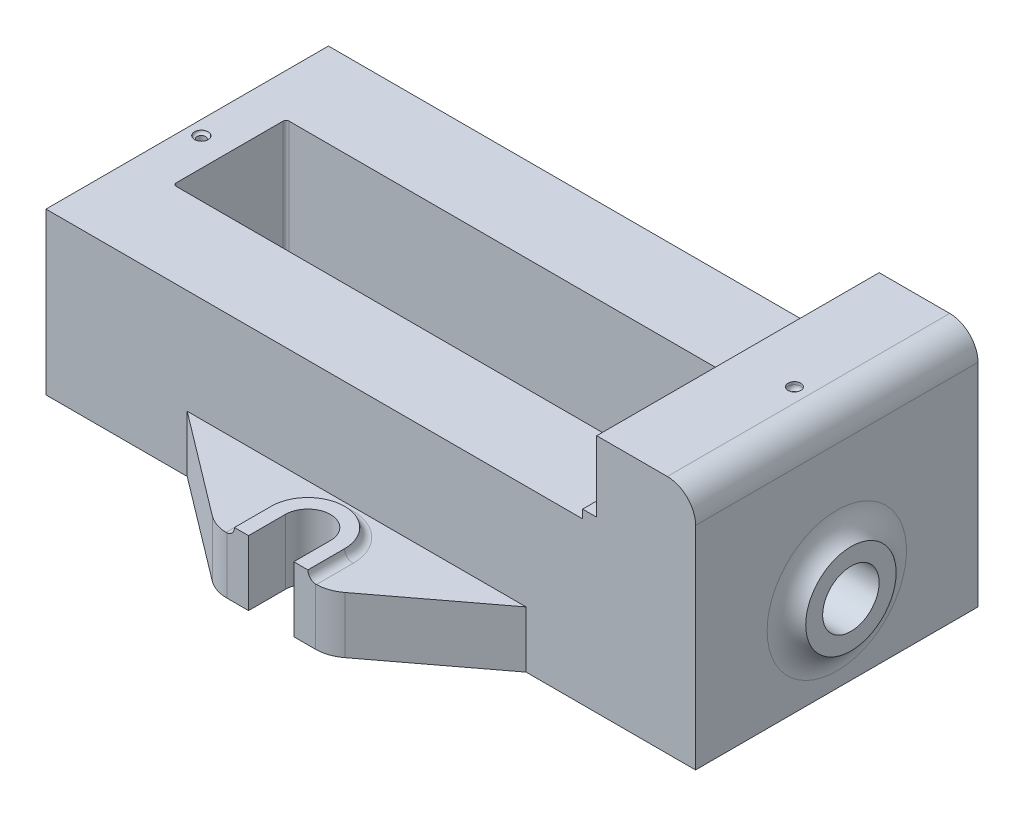
SolidWorks part; units mm, degrees
ref_plane "Front Plane" through (0, 0, 0) normal (0, 0, 1) x (1, 0, 0)
ref_plane "Top Plane" through (0, 0, 0) normal (0, 1, 0) x (1, 0, 0)
ref_plane "Right Plane" through (0, 0, 0) normal (1, 0, 0) x (0, 0, -1)
sketch "Sketch1" plane through (0, 0, 0) normal (0, 0, 1) x (1, 0, 0)
  line L0 (-148.8487, 0) -> (180.479, 0) construction
  line L1 (146.3044, 0) -> (146.3044, 75)
  line L2 (136.3044, 85) -> (111.3044, 85)
  line L3 (111.3044, 85) -> (111.3044, 60)
  line L4 (111.3044, 60) -> (106.3044, 60)
  line L5 (106.3044, 60) -> (106.3044, 57)
  line L6 (106.3044, 57) -> (-83.6956, 57)
  line L7 (-83.6956, 57) -> (-83.6956, 0)
  line L8 (-83.6956, 0) -> (146.3044, 0)
  arc A0 (136.3044, 85) -> (146.3044, 75) centre (136.3044, 75) cw
  point P13 (146.3044, 85)
  point P20 (153.9046, 30)
  dimension "D6" = 10
  dimension "D1" = 85
  dimension "D2" = 230
  dimension "D3" = 40
  dimension "D4" = 5
  dimension "D5" = 25
  dimension "D7" = 57
  dimension "D8" = 30
extrude "Boss-Extrude1" add sketch "Sketch1" along normal blind 100
sketch "Sketch2" plane through (146.3044, 0, 0) normal (1, 0, 0) x (0, 0, -1)
  line L0 (-100, 0) -> (0, 0) construction
  circle A0 centre (-50, 30) radius 16
  point P0 (-50, 0)
  dimension "D2" = 32
  dimension "D1" = 30
extrude "Boss-Extrude2" add sketch "Sketch2" along normal blind 5
fillet "Fillet1" radius 10 1 edges at (146.3044, 30, 66)
sketch "Sketch3" plane through (-83.6956, 0, 0) normal (-1, 0, 0) x (0, 0, 1)
  line L0 (50, 57) -> (50, 0) construction
  line L1 (100, 57) -> (0, 57) construction
  line L2 (100, 0) -> (0, 0) construction
  circle A1 centre (50, 30) radius 16
  dimension "D3" = 32
  dimension "D1" = 30
extrude "Boss-Extrude3" add sketch "Sketch3" along normal blind 5
fillet "Fillet2" radius 10 1 edges at (-83.6956, 46, 50)
sketch "Sketch4" plane through (-88.6956, 0, 0) normal (-1, 0, 0) x (0, 0, 1)
  circle A0 centre (50, 30) radius 5
  dimension "D1" = 10
extrude "Cut-Extrude1" cut sketch "Sketch4" against normal blind 20
sketch "Sketch5" plane through (0, 57, 0) normal (0, 1, 0) x (1, 0, 0)
  line L0 (-83.6956, -50) -> (106.3044, -50) construction
  line L1 (-83.6956, -100) -> (-83.6956, 0) construction
  line L2 (106.3044, -100) -> (106.3044, 0) construction
  line L4 (-67.6956, -30) -> (105.3044, -30)
  line L5 (-68.6956, -31) -> (-68.6956, -69)
  line L6 (-67.6956, -70) -> (105.3044, -70)
  line L7 (106.3044, -31) -> (106.3044, -69)
  line L8 (-68.6956, -30) -> (-68.1706, -30.12) construction
  line L9 (-68.6956, -70) -> (-68.1706, -69.88) construction
  line L10 (105.7794, -30.12) -> (106.3044, -30) construction
  line L11 (105.7794, -69.88) -> (106.3044, -70) construction
  arc A0 (106.3044, -31) -> (105.3044, -30) centre (105.3044, -31) ccw
  arc A1 (106.3044, -69) -> (105.3044, -70) centre (105.3044, -69) cw
  arc A2 (-67.6956, -70) -> (-68.6956, -69) centre (-67.6956, -69) cw
  arc A3 (-68.6956, -31) -> (-67.6956, -30) centre (-67.6956, -31) cw
  point P6 (18.8044, -50)
  dimension "D3" = 1
  dimension "D1" = 40
  dimension "D2" = 15
extrude "Cut-Extrude2" cut sketch "Sketch5" against normal through all
sketch "Sketch6" plane through (151.3044, 0, 0) normal (1, 0, 0) x (0, 0, -1)
  circle A0 centre (-50, 30) radius 10
  dimension "D1" = 20
extrude "Cut-Extrude3" cut sketch "Sketch6" against normal up to next
sketch "Sketch7" plane through (0, 0, 0) normal (0, -1, 0) x (1, 0, 0)
  line L0 (26.3044, 127.7371) -> (26.3044, -29.0287) construction
  line L3 (-88.6956, 66) -> (-88.6956, 34) construction
  line L4 (-33.6956, 100) -> (86.3044, 100)
  line L5 (-83.6956, 100) -> (146.3044, 100) construction
  line L6 (86.3044, 100) -> (49.7849, 127.6407)
  line L7 (41.9393, 130.275) -> (34.3044, 130.275)
  line L8 (34.3044, 130.275) -> (34.3044, 117.275)
  line L9 (-83.6956, 50) -> (146.3044, 50) construction
  line L10 (-33.6956, 100) -> (2.8239, 127.6407)
  line L11 (10.6694, 130.275) -> (18.3044, 130.275)
  line L12 (18.3044, 130.275) -> (18.3044, 117.275)
  line L13 (-83.6956, 100) -> (-83.6956, 0) construction
  line L14 (146.3044, 100) -> (146.3044, 0) construction
  line L15 (18.3044, -30.275) -> (18.3044, -17.275)
  line L16 (10.6694, -30.275) -> (18.3044, -30.275)
  line L17 (-33.6956, 0) -> (2.8239, -27.6407)
  line L18 (34.3044, -30.275) -> (34.3044, -17.275)
  line L19 (41.9393, -30.275) -> (34.3044, -30.275)
  line L20 (86.3044, 0) -> (49.7849, -27.6407)
  line L21 (-33.6956, 0) -> (86.3044, 0)
  arc A0 (34.3044, 117.275) -> (18.3044, 117.275) centre (26.3044, 117.275) cw
  arc A1 (49.7849, 127.6407) -> (41.9393, 130.275) centre (41.9393, 117.275) ccw
  arc A2 (2.8239, 127.6407) -> (10.6694, 130.275) centre (10.6694, 117.275) cw
  arc A3 (2.8239, -27.6407) -> (10.6694, -30.275) centre (10.6694, -17.275) ccw
  arc A4 (49.7849, -27.6407) -> (41.9393, -30.275) centre (41.9393, -17.275) cw
  arc A5 (34.3044, -17.275) -> (18.3044, -17.275) centre (26.3044, -17.275) ccw
  point P15 (46.3044, 130.275)
  point P39 (46.3044, -30.275)
  dimension "D4" = 8
  dimension "D5" = 13
  dimension "D1" = 115
  dimension "D3" = 20
  dimension "D6" = 13
extrude "Boss-Extrude5" add sketch "Sketch7" against normal blind 20
sketch "Sketch8" plane through (0, 20, 0) normal (0, 1, 0) x (1, 0, 0)
  line L0 (39.3044, 17.275) -> (39.3044, 30.275)
  line L1 (34.3044, 30.275) -> (41.9393, 30.275) construction
  line L3 (39.3044, 30.275) -> (34.3044, 30.275)
  line L5 (34.3044, 30.275) -> (34.3044, 17.5565)
  line L6 (34.3044, 17.275) -> (34.3044, 30.275) construction
  line L7 (13.3044, 17.275) -> (13.3044, 30.275)
  line L8 (10.6694, 30.275) -> (18.3044, 30.275) construction
  line L9 (13.3044, 30.275) -> (18.3044, 30.275)
  line L11 (18.3044, 30.275) -> (18.3044, 17.275)
  line L19 (2.8239, 27.6407) -> (-33.6956, 0)
  line L20 (-33.6956, 0) -> (86.3044, 0)
  line L21 (86.3044, 0) -> (49.7849, 27.6407)
  line L22 (41.9393, 30.275) -> (34.3044, 30.275)
  line L23 (34.3044, 30.275) -> (34.3044, 17.275)
  line L24 (18.3044, 17.275) -> (18.3044, 30.275)
  line L25 (18.3044, 30.275) -> (10.6694, 30.275)
  line L30 (34.3044, 17.5565) -> (34.3044, 17.275)
  arc A1 (13.3044, 17.275) -> (39.3044, 17.275) centre (26.3044, 17.275) ccw
  arc A3 (18.3044, 17.275) -> (34.3044, 17.275) centre (26.3044, 17.275) ccw
  arc A7 (10.6694, 30.275) -> (2.8239, 27.6407) centre (10.6694, 17.275) ccw
  arc A8 (49.7849, 27.6407) -> (41.9393, 30.275) centre (41.9393, 17.275) ccw
  arc A9 (18.3044, 17.275) -> (34.3044, 17.275) centre (26.3044, 17.275) ccw
  circle A12 centre (26.3044, 17.275) radius 8
  line M6 (41.9393, 30.275) -> (34.3044, 30.275)
  line M7 (34.3044, 30.275) -> (34.3044, 17.275)
  arc M8 (34.3044, 17.275) -> (18.3044, 17.275) centre (26.3044, 17.275) cw
  line M9 (18.3044, 17.275) -> (18.3044, 30.275)
  line M10 (18.3044, 30.275) -> (10.6694, 30.275)
  dimension "D1" = 13
  dimension "D2" = 0
extrude "Boss-Extrude6" add sketch "Sketch8" along normal blind 3 contours L7 A1 L0 M6 M7 M8 M9 M10 region at (26.3044, 20, -4.6427)
fillet "Fillet3" radius 3 3 edges at (39.3044, 20, -23.775) (26.3044, 20, -4.275) (13.3044, 20, -23.775)
sketch "Sketch10" plane through (0, 20, 0) normal (0, 1, 0) x (1, 0, 0)
  line L0 (13.3044, -117.275) -> (13.3044, -130.275)
  line L1 (18.3044, -130.275) -> (10.6694, -130.275) construction
  line L2 (13.3044, -130.275) -> (18.3044, -130.275)
  line L3 (18.3044, -117.275) -> (18.3044, -130.275) construction
  line L4 (18.3044, -130.275) -> (18.3044, -117.275)
  line L5 (39.3044, -117.275) -> (39.3044, -130.275)
  line L6 (41.9393, -130.275) -> (34.3044, -130.275) construction
  line L7 (39.3044, -130.275) -> (34.3044, -130.275)
  line L8 (34.3044, -130.275) -> (34.3044, -117.275)
  arc A0 (39.3044, -117.275) -> (13.3044, -117.275) centre (26.3044, -117.275) ccw
  arc A1 (34.3044, -117.275) -> (18.3044, -117.275) centre (26.3044, -117.275) ccw
  arc A2 (34.3044, -117.275) -> (18.3044, -117.275) centre (26.3044, -117.275) ccw construction
  line M5 (10.6694, -130.275) -> (18.3044, -130.275)
  line M6 (18.3044, -130.275) -> (18.3044, -117.275)
  arc M7 (18.3044, -117.275) -> (34.3044, -117.275) centre (26.3044, -117.275) cw
  line M8 (34.3044, -117.275) -> (34.3044, -130.275)
  line M9 (34.3044, -130.275) -> (41.9393, -130.275)
  dimension "D1" = 13
extrude "Boss-Extrude7" add sketch "Sketch10" along normal blind 3 contours L5 A0 L0 M5 M6 M7 M8 M9 region at (26.3044, 20, 104.6427)
fillet "Fillet4" radius 3 3 edges at (13.3044, 20, 123.775) (26.3044, 20, 104.275) (39.3044, 20, 123.775)
sketch "Sketch11" plane through (0, 57, 0) normal (0, 1, 0) x (1, 0, 0)
  line L0 (-83.6956, -50) -> (109.1641, -50) construction
  line L1 (-83.6956, -100) -> (-83.6956, 0) construction
  line L2 (-88.6956, -45) -> (-88.6956, -55) construction
  point P4 (-78.6956, -50)
  dimension "D1" = 10
sketch "Sketch14" plane through (0, 57, 0) normal (0, 1, 0) x (1, 0, 0)
  circle A0 centre (-78.6956, -50) radius 1.5
  dimension "D1" = 3
extrude "Cut-Extrude4" cut sketch "Sketch14" against normal up to next
sketch "Sketch15" plane through (0, 57, 0) normal (0, 1, 0) x (1, 0, 0)
  circle A0 centre (-78.6956, -50) radius 2.4118
extrude "Cut-Extrude5" cut sketch "Sketch15" against normal blind 1
fillet "Fillet5" radius 1 1 edges at (-81.1074, 56, 50)
sketch "Sketch16" plane through (111.3044, 0, 0) normal (-1, 0, 0) x (0, 0, 1)
  line L0 (50, 85) -> (50, 0) construction
  line L1 (100, 85) -> (0, 85) construction
  line L2 (100, 0) -> (0, 0) construction
  line L3 (100, 60) -> (0, 60) construction
  circle A0 centre (80, 72.5) radius 2.5
  circle A1 centre (20, 72.5) radius 2.5
  point P6 (80, 72.5)
  dimension "D3" = 5
  dimension "D1" = 12.5
  dimension "D2" = 30
extrude "Cut-Extrude6" cut sketch "Sketch16" against normal blind 13
sketch "Sketch18" plane through (111.3044, 0, 0) normal (-1, 0, 0) x (0, 0, 1)
  circle A0 centre (80, 72.5) radius 3
  dimension "D1" = 6
extrude "Cut-Extrude7" cut sketch "Sketch18" against normal blind 10
fillet "Fillet6" radius 1 1 edges at (121.3044, 72.5, 83)
sketch "Sketch20" plane through (111.3044, 0, 0) normal (-1, 0, 0) x (0, 0, 1)
  circle A0 centre (20, 72.5) radius 3
  dimension "D1" = 6
extrude "Cut-Extrude8" cut sketch "Sketch20" against normal blind 10
fillet "Fillet7" radius 1 1 edges at (121.3044, 72.5, 23)
sketch "Sketch21" plane through (0, 85, 0) normal (0, 1, 0) x (1, 0, 0)
  line L0 (111.3044, -50) -> (136.3044, -50) construction
  line L1 (111.3044, -100) -> (111.3044, 0) construction
  line L2 (136.3044, -100) -> (136.3044, 0) construction
  line L3 (151.3044, -66) -> (151.3044, -34) construction
  circle A0 centre (131.3044, -50) radius 1.5
  dimension "D2" = 3
  dimension "D1" = 20
extrude "Cut-Extrude9" cut sketch "Sketch21" against normal up to next
sketch "Sketch22" plane through (0, 85, 0) normal (0, 1, 0) x (1, 0, 0)
  circle A0 centre (131.3044, -50) radius 2.25
  dimension "D1" = 4.5
extrude "Cut-Extrude10" cut sketch "Sketch22" against normal blind 2.5
fillet "Fillet8" radius 2 1 edges at (131.3044, 82.5, 52.25)
sketch "Sketch23" plane through (0, 0, 0) normal (0, -1, 0) x (1, 0, 0)
  line L0 (-83.6956, 50) -> (109.1641, 50) construction
  line L1 (-68.6956, 76) -> (106.3044, 76)
  line L2 (-68.6956, 76) -> (-68.6956, 24)
  line L3 (-68.6956, 24) -> (106.3044, 24)
  line L4 (106.3044, 76) -> (106.3044, 24)
  line L5 (106.3044, 69) -> (106.3044, 31) construction
  line L6 (-83.6956, 50) -> (109.1641, 50) construction
  line L7 (-68.6956, 31) -> (-68.6956, 69) construction
  point P0 (12.7343, 50)
  point P15 (106.3044, 50)
  dimension "D1" = 0
  dimension "D2" = 0
  dimension "D3" = 52
extrude "Cut-Extrude11" cut sketch "Sketch23" against normal blind 13
sketch "Sketch25" plane through (0, 0, 0) normal (0, -1, 0) x (1, 0, 0)
  line L0 (-83.6956, 50) -> (109.1641, 50) construction
  line L1 (-68.6956, 80) -> (106.3044, 80)
  line L2 (-68.6956, 80) -> (-68.6956, 20)
  line L3 (-68.6956, 20) -> (106.3044, 20)
  line L4 (106.3044, 80) -> (106.3044, 20)
  line L5 (-68.6956, 24) -> (-68.6956, 76) construction
  line L6 (106.3044, 76) -> (106.3044, 24) construction
  point P0 (28.4174, 50)
  point P11 (106.3044, 50)
  dimension "D1" = 0
  dimension "D2" = 0
  dimension "D3" = 60
extrude "Cut-Extrude12" cut sketch "Sketch25" against normal blind 10
fillet "Fillet9" radius 5 2 edges at (18.8044, 10, 80) (18.8044, 10, 20)
